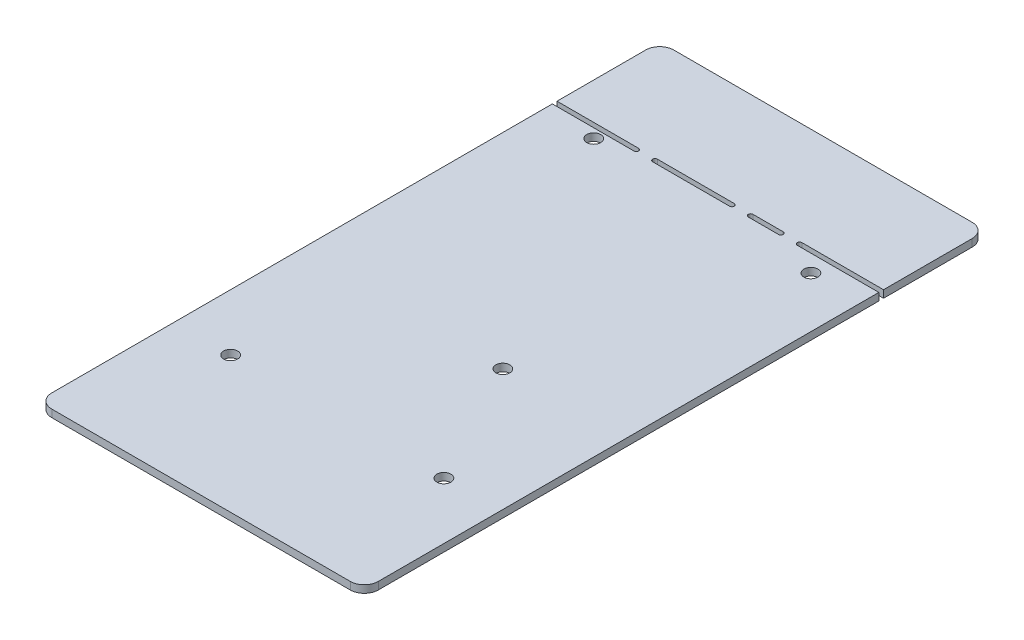
SolidWorks part; units mm, degrees
material "ｴﾎﾟｷｼ樹脂(充填剤なし)"
ref_plane "正面" through (0, 0, 0) normal (0, 0, 1) x (1, 0, 0)
ref_plane "平面" through (0, 0, 0) normal (0, 1, 0) x (1, 0, 0)
ref_plane "右側面" through (0, 0, 0) normal (1, 0, 0) x (0, 0, -1)
sketch "ｽｹｯﾁ1" plane through (0, 0, 0) normal (0, 1, 0) x (1, 0, 0)
  line L1 (-35, 66.67) -> (35, 66.67)
  line L2 (-35, 66.67) -> (-35, -66.67)
  line L3 (-35, -66.67) -> (35, -66.67)
  line L4 (35, 66.67) -> (35, -66.67)
  line L5 (-35, 66.67) -> (35, -66.67) construction
  line L6 (-35, -66.67) -> (35, 66.67) construction
  point P0 (0, 0)
  dimension "D1" = 133.34
  dimension "D2" = 70
extrude "ﾎﾞｽ - 押し出し1" add sketch "ｽｹｯﾁ1" along normal blind 1.6
sketch "ｽｹｯﾁ2" plane through (0, 1.6, 0) normal (0, 1, 0) x (1, 0, 0)
  line L0 (0, 0) -> (0, -66.67) construction
  line L1 (-35, -66.67) -> (35, -66.67) construction
  line L2 (0, -37.46) -> (-22.86, -37.46) construction
  line L3 (-35, 66.67) -> (-35, -66.67) construction
  line L4 (-35, 44.65) -> (-17, 44.65)
  line L5 (-35, 44.65) -> (-35, 43.65)
  line L6 (-35, 43.65) -> (-17, 43.65)
  line L7 (-17, 44.65) -> (-17, 43.65)
  line L8 (35, 66.67) -> (-35, 66.67) construction
  line L9 (17, 44.65) -> (17, 43.65)
  line L10 (35, 43.65) -> (17, 43.65)
  line L11 (35, 44.65) -> (35, 43.65)
  line L12 (35, 44.65) -> (17, 44.65)
  line L13 (-17, 44.65) -> (17, 44.65) construction
  line L14 (-17, 43.65) -> (17, 43.65) construction
  line L16 (-14, 44.65) -> (3.5, 44.65)
  line L17 (-14, 44.65) -> (-14, 43.65)
  line L18 (-14, 43.65) -> (3.5, 43.65)
  line L19 (3.5, 44.65) -> (3.5, 43.65)
  line L20 (6.5, 44.65) -> (14, 44.65)
  line L21 (6.5, 44.65) -> (6.5, 43.65)
  line L22 (6.5, 43.65) -> (14, 43.65)
  line L23 (14, 44.65) -> (14, 43.65)
  circle A0 centre (-22.86, -37.46) radius 1.5
  circle A1 centre (22.86, -37.46) radius 1.5
  circle A2 centre (-24.13, 41.65) radius 1.5
  circle A3 centre (24.13, 39.95) radius 1.5
  circle A4 centre (8.89, -10.85) radius 1.5
  dimension "D1" = 45.72
  dimension "D3" = 3
  dimension "D4" = 3.7
  dimension "D2" = 29.21
  dimension "D5" = 22.02
  dimension "D6" = 1
  dimension "D7" = 2
  dimension "D8" = 18
  dimension "D9" = 24.13
  dimension "D10" = 24.13
  dimension "D11" = 3
  dimension "D12" = 3
  dimension "D13" = 3
  dimension "D14" = 7.5
  dimension "D15" = 15.24
  dimension "D16" = 50.8
extrude "ｶｯﾄ - 押し出し1" cut sketch "ｽｹｯﾁ2" against normal through all
fillet "ﾌｨﾚｯﾄ1" radius 3 4 edges at (35, 0.8, 66.67) (-35, 0.8, 66.67) (35, 0.8, -66.67) (-35, 0.8, -66.67)
fillet "ﾌｨﾚｯﾄ2" radius 0.5 12 edges at (17, 0.8, -44.65) (17, 0.8, -43.65) (14, 0.8, -43.65) (14, 0.8, -44.65) (6.5, 0.8, -44.65) (6.5, 0.8, -43.65) (3.5, 0.8, -43.65) (3.5, 0.8, -44.65) (-17, 0.8, -44.65) (-17, 0.8, -43.65) (-14, 0.8, -43.65) (-14, 0.8, -44.65)
